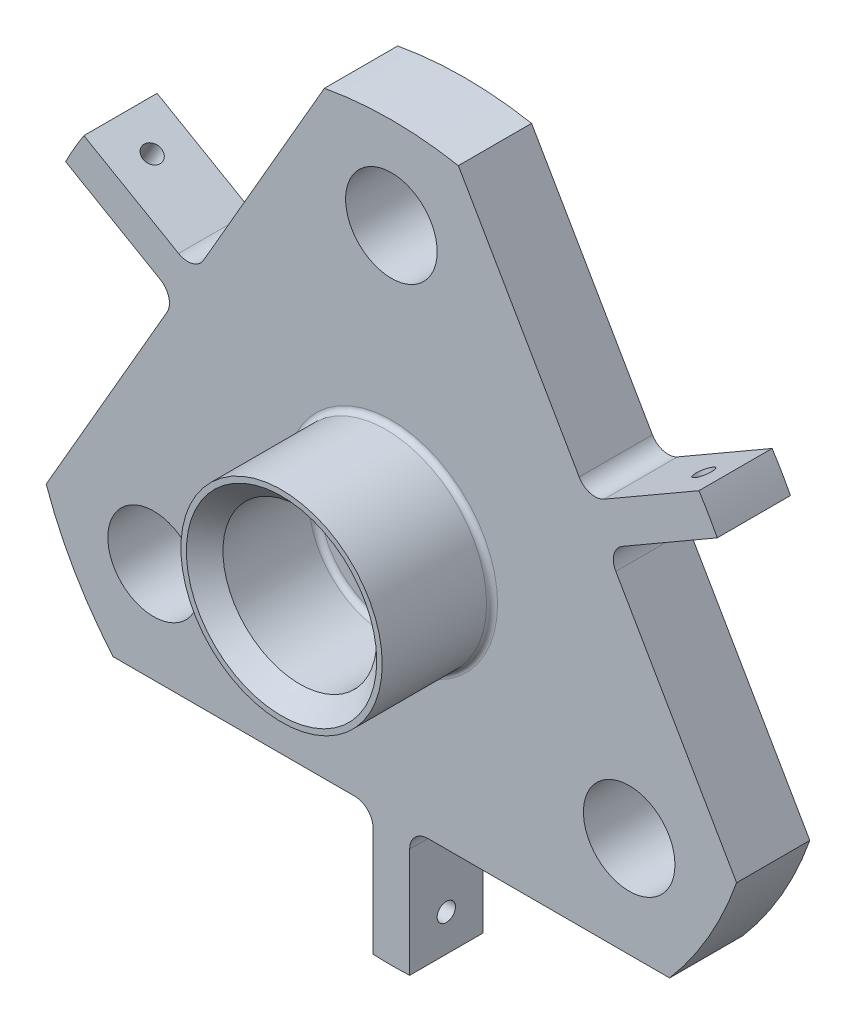
SolidWorks part; units mm, degrees
ref_plane "Front Plane" through (0, 0, 0) normal (0, 0, 1) x (1, 0, 0)
ref_plane "Top Plane" through (0, 0, 0) normal (0, 1, 0) x (1, 0, 0)
ref_plane "Right Plane" through (0, 0, 0) normal (1, 0, 0) x (0, 0, -1)
sketch "Sketch1" plane through (0, 0, 0) normal (0, 0, 1) x (1, 0, 0)
  circle A0 centre (0, 0) radius 21
  circle A1 centre (0, 0) radius 100
  circle A2 centre (0, 0) radius 27.5
  dimension "D1" = 42
  dimension "D2" = 200
  dimension "D3" = 55
extrude "Boss-Extrude1" add sketch "Sketch1" along normal blind 50 contours A2 A0 region at (-26.7222, 0, 0)
extrude "Boss-Extrude2" add sketch "Sketch1<3>" along normal blind 20 contours A1 A2 | A0 region at (-97.1716, 0, 0)
sketch "Sketch1<3>" plane through (0, 0, 0) normal (0, 0, 1) x (1, 0, 0) same geometry as "Sketch1"
chamfer "Chamfer1" distance 5 angle 45 1 edges at (21, 0, 50)
fillet "Fillet1" radius 1.5 2 edges at (27.5, 0, 20) (21, 0, 20)
sketch "Sketch10" plane through (0, 0, 20) normal (0, 0, 1) x (1, 0, 0)
  circle A0 centre (0, 75) radius 12.5
  circle A1 centre (64.9519, -37.5) radius 12.5
  circle A2 centre (-64.9519, -37.5) radius 12.5
  point P7 (0, 75)
  point P12 (0, 0)
  dimension "D1" = 25
  dimension "D3" = 3
  dimension "D2" = 75
extrude "Cut-Extrude1" cut sketch "Sketch10" against normal blind 20
sketch "Sketch12" plane through (0, 0, 0) normal (0, 0, -1) x (-1, 0, 0)
  line L0 (-10, -100) -> (10, -100)
  line L1 (-100, 100) -> (100, 100)
  line L2 (-100, 100) -> (-100, -100)
  line L3 (-100, -100) -> (100, -100)
  line L4 (100, 100) -> (100, -100)
  line L5 (-100, 100) -> (100, -100) construction
  line L6 (-100, -100) -> (100, 100) construction
  line L7 (-10, -130) -> (-10, -70) construction
  line L8 (10, -130) -> (10, -70) construction
  line L9 (-15, -130) -> (-15, -70)
  line L10 (-5, -130) -> (-5, -70)
  line L11 (-61.2917, 23.8397) -> (-91.6025, 41.3397)
  line L12 (5, -130) -> (5, -70)
  line L13 (15, -130) -> (15, -70)
  line L14 (-10, -65) -> (-100, -65)
  line L15 (-10, -65) -> (-10, -100)
  line L16 (-10, -100) -> (-100, -100)
  line L17 (-100, -65) -> (-100, -100)
  line L18 (10, -65) -> (100, -65)
  line L19 (10, -65) -> (10, -100)
  line L20 (10, -100) -> (100, -100)
  line L21 (100, -65) -> (100, -100)
  line L22 (-61.2917, 23.8397) -> (-106.2917, -54.1025)
  line L23 (-106.2917, -54.1025) -> (-136.6025, -36.6025)
  line L24 (-91.6025, 41.3397) -> (-136.6025, -36.6025)
  line L25 (-51.2917, 41.1603) -> (-81.6025, 58.6603)
  line L26 (-51.2917, 41.1603) -> (-6.2917, 119.1025)
  line L27 (-6.2917, 119.1025) -> (-36.6025, 136.6025)
  line L28 (-81.6025, 58.6603) -> (-36.6025, 136.6025)
  line L29 (-110.0833, 69.3301) -> (-58.1218, 39.3301)
  line L30 (-105.0833, 77.9904) -> (-53.1218, 47.9904)
  line L31 (-120.0833, 52.0096) -> (-68.1218, 22.0096)
  line L32 (-115.0833, 60.6699) -> (-63.1218, 30.6699)
  line L33 (-107.5833, 73.6603) -> (-55.6218, 43.6603) construction
  line L34 (-117.5833, 56.3397) -> (-65.6218, 26.3397) construction
  line L35 (51.2917, 41.1603) -> (81.6025, 58.6603)
  line L36 (51.2917, 41.1603) -> (6.2917, 119.1025)
  line L37 (6.2917, 119.1025) -> (36.6025, 136.6025)
  line L38 (81.6025, 58.6603) -> (36.6025, 136.6025)
  line L39 (61.2917, 23.8397) -> (91.6025, 41.3397)
  line L40 (61.2917, 23.8397) -> (106.2917, -54.1025)
  line L41 (106.2917, -54.1025) -> (136.6025, -36.6025)
  line L42 (91.6025, 41.3397) -> (136.6025, -36.6025)
  line L43 (115.0833, 60.6699) -> (63.1218, 30.6699)
  line L44 (120.0833, 52.0096) -> (68.1218, 22.0096)
  line L45 (105.0833, 77.9904) -> (53.1218, 47.9904)
  line L46 (110.0833, 69.3301) -> (58.1218, 39.3301)
  line L47 (117.5833, 56.3397) -> (65.6218, 26.3397) construction
  line L48 (107.5833, 73.6603) -> (55.6218, 43.6603) construction
  arc A0 (-15, -130) -> (-5, -130) centre (-10, -130) ccw
  arc A1 (-5, -70) -> (-15, -70) centre (-10, -70) ccw
  arc A2 (5, -130) -> (15, -130) centre (10, -130) ccw
  arc A3 (15, -70) -> (5, -70) centre (10, -70) ccw
  arc A4 (-105.0833, 77.9904) -> (-110.0833, 69.3301) centre (-107.5833, 73.6603) ccw
  arc A5 (-58.1218, 39.3301) -> (-53.1218, 47.9904) centre (-55.6218, 43.6603) ccw
  arc A6 (-115.0833, 60.6699) -> (-120.0833, 52.0096) centre (-117.5833, 56.3397) ccw
  arc A7 (-68.1218, 22.0096) -> (-63.1218, 30.6699) centre (-65.6218, 26.3397) ccw
  arc A8 (120.0833, 52.0096) -> (115.0833, 60.6699) centre (117.5833, 56.3397) ccw
  arc A9 (63.1218, 30.6699) -> (68.1218, 22.0096) centre (65.6218, 26.3397) ccw
  arc A10 (110.0833, 69.3301) -> (105.0833, 77.9904) centre (107.5833, 73.6603) ccw
  arc A11 (53.1218, 47.9904) -> (58.1218, 39.3301) centre (55.6218, 43.6603) ccw
  circle A12 centre (0, 75) radius 12.5 construction
  point P0 (0, 0)
  point P9 (0, -100)
  point P13 (-10, -100)
  point P20 (10, -100)
  point P38 (-81.6025, 58.6603)
  point P45 (-91.6025, 41.3397)
  point P60 (91.6025, 41.3397)
  point P67 (81.6025, 58.6603)
  point P76 (0, 0)
  dimension "D1" = 200
  dimension "D4" = 5
  dimension "D5" = 5
  dimension "D2" = 20
  dimension "D3" = 60
  dimension "D6" = 60
  dimension "D7" = 3
  dimension "D8" = 35
extrude "Cut-Extrude3" cut sketch "Sketch12" against normal through all contours L28 L27 L26 L25 | L30 A5 L29 A4 | L31 A7 L32 A6 | L24 L23 L22 L11 | L38 L37 L36 L35 | L46 A11 L45 A10 | L43 A9 L44 A8 | L42 L41 L40 L39 | L20 L19 L18 L21 | L16 L15 L14 L17 | L9 A1 L10 A0 | L13 A3 L12 A2
sketch "Sketch13" plane through (2.5, -4.3301, 0) normal (0.5, -0.866, 0) x (0.866, 0.5, 0)
  line L0 (89.8749, 10) -> (99.8749, 10) construction
  line L1 (99.8749, 0) -> (99.8749, 20) construction
  line L2 (70, 20) -> (99.8749, 20) construction
  circle A0 centre (89.8749, 10) radius 2.5
  dimension "D1" = 5
  dimension "D2" = 10
  dimension "D3" = 10
extrude "Cut-Extrude4" cut sketch "Sketch13" against normal through all
sketch "Sketch14" plane through (-5, 0, 0) normal (-1, 0, 0) x (0, 0, 1)
  line L0 (10, -89.8749) -> (10, -99.8749) construction
  line L1 (0, -99.8749) -> (20, -99.8749) construction
  line L2 (20, -70) -> (20, -99.8749) construction
  circle A0 centre (10, -89.8749) radius 2.5
  dimension "D1" = 5
  dimension "D2" = 10
  dimension "D3" = 10
extrude "Cut-Extrude5" cut sketch "Sketch14" against normal through all
sketch "Sketch15" plane through (-2.5, -4.3301, 0) normal (-0.5, -0.866, 0) x (0.866, -0.5, 0)
  line L0 (-70, 20) -> (-99.8749, 20) construction
  line L1 (-99.8749, 0) -> (-99.8749, 20) construction
  circle A0 centre (-89.8749, 10) radius 2.5
  point P2 (0, 0)
  dimension "D1" = 5
  dimension "D2" = 10
  dimension "D3" = 10
extrude "Cut-Extrude6" cut sketch "Sketch15" against normal through all
